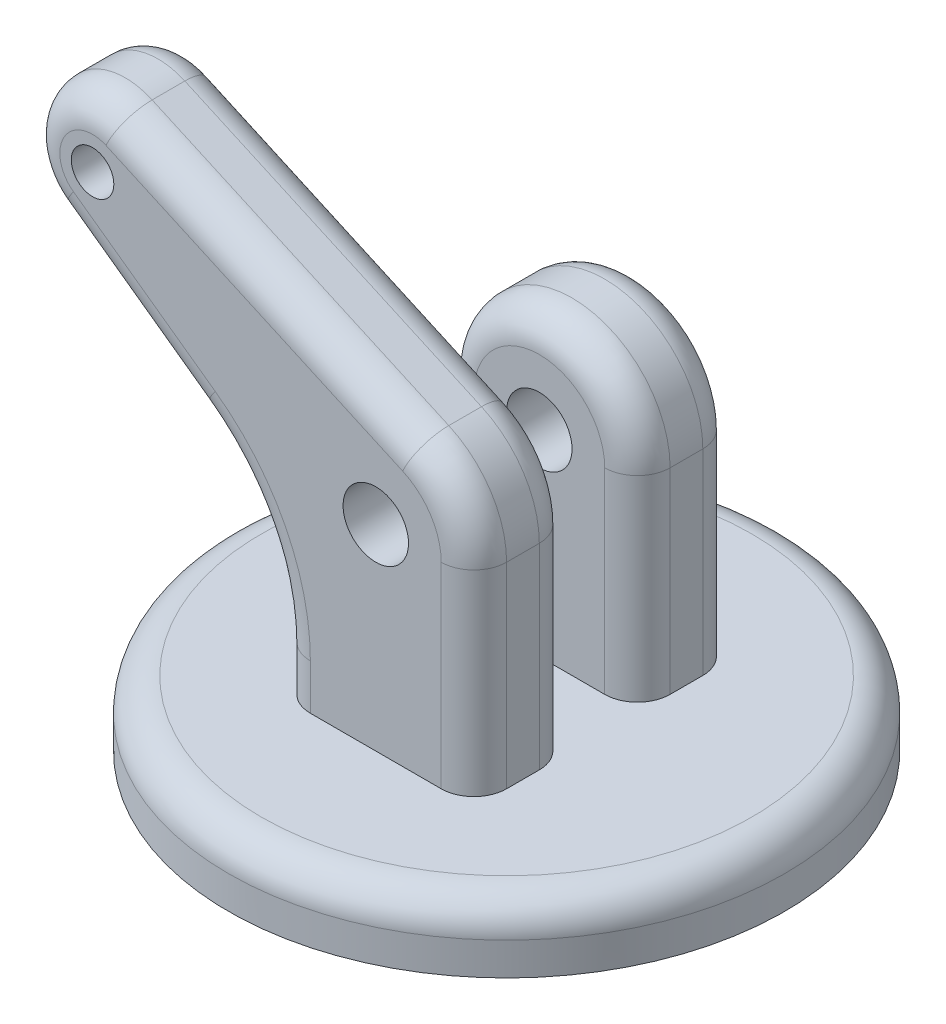
SolidWorks part; units mm, degrees
ref_plane "Front Plane" through (0, 0, 0) normal (0, 0, 1) x (1, 0, 0)
ref_plane "Top Plane" through (0, 0, 0) normal (0, 1, 0) x (1, 0, 0)
ref_plane "Right Plane" through (0, 0, 0) normal (1, 0, 0) x (0, 0, -1)
sketch "Sketch1" plane through (0, 0, 0) normal (0, 1, 0) x (1, 0, 0)
  line L1 (-20, 30) -> (20, 30)
  line L2 (-20, 30) -> (-20, -30)
  line L3 (-20, -30) -> (20, -30)
  line L4 (20, 30) -> (20, -30)
  line L5 (-20, 30) -> (20, -30) construction
  line L6 (-20, -30) -> (20, 30) construction
  point P0 (0, 0)
  dimension "D1" = 40
  dimension "D2" = 60
extrude "Boss-Extrude1" add sketch "Sketch1" along normal blind 10
sketch "Sketch2" plane through (0, 0, 0) normal (0, 1, 0) x (1, 0, 0)
  line L0 (-20, 0) -> (20, 0) construction
  line L1 (-20, 30) -> (-20, -30) construction
  line L2 (20, -30) -> (20, 30) construction
  line L4 (-15, 20) -> (15, 20)
  line L5 (-15, 20) -> (-15, -20)
  line L6 (-15, -20) -> (15, -20)
  line L7 (15, 20) -> (15, -20)
  line L8 (-15, 20) -> (15, -20) construction
  line L9 (-15, -20) -> (15, 20) construction
  point P6 (0, 0)
  dimension "D1" = 30
  dimension "D2" = 40
extrude "Boss-Extrude2" add sketch "Sketch2" along normal blind 40
sketch "Sketch6" plane through (0, 0, 0) normal (0, 0, 1) x (1, 0, 0)
  line L0 (-15, 40) -> (15, 40) construction
  circle A0 centre (0, 40) radius 15
  circle A1 centre (0, 40) radius 5
  dimension "D1" = 10
extrude "Boss-Extrude4" add sketch "Sketch6" against normal mid plane 40
sketch "Sketch7" plane through (0, 0, 0) normal (0, 0, 1) x (1, 0, 0)
  line L0 (-5, 40) -> (5, 40) construction
  circle A0 centre (0, 40) radius 5
extrude "Cut-Extrude2" cut sketch "Sketch7" against normal mid plane 60
sketch "Sketch8" plane through (0, 0, 0) normal (0, 1, 0) x (1, 0, 0)
  line L0 (-15, 0) -> (15, 0) construction
  line L1 (-15, -20) -> (-15, 20) construction
  line L2 (15, 20) -> (15, -20) construction
  line L4 (-15, 5) -> (15, 5)
  line L5 (-15, 5) -> (-15, -5)
  line L6 (-15, -5) -> (15, -5)
  line L7 (15, 5) -> (15, -5)
  line L8 (-15, 5) -> (15, -5) construction
  line L9 (-15, -5) -> (15, 5) construction
  point P6 (0, 0)
  dimension "D1" = 10
extrude "Cut-Extrude3" cut sketch "Sketch8" along normal blind 50 from surface starting at face at (0, 10, 0)
sketch "Sketch10" plane through (0, 0, 0) normal (0, 0, 1) x (1, 0, 0)
  line L0 (0, 40) -> (-66.6019, 40) construction
  line L1 (0, 40) -> (-43.3013, 65) construction
  line L2 (-49.1422, 56.8832) -> (-8.7614, 27.8247)
  line L3 (-39.1924, 74.1168) -> (6.1634, 53.6753)
  arc A0 (-39.1924, 74.1168) -> (-49.1422, 56.8832) centre (-43.3013, 65) ccw
  circle A1 centre (-43.3013, 65) radius 3.25
  circle A2 centre (0, 40) radius 15 construction
  arc A3 (-8.7614, 27.8247) -> (6.1634, 53.6753) centre (0, 40) cw
  dimension "D3" = 20
  dimension "D4" = 6.5
  dimension "D1" = 30
  dimension "D2" = 50
extrude "Boss-Extrude5" add sketch "Sketch10" along normal blind 15 from surface starting at face at (0, 28.75, 5)
fillet "Fillet1" radius 30 1 edges at (-15, 32.3141, 12.5)
fillet "Fillet2" radius 5 14 edges at (-15, 13.4711, 5) (-18.3009, 30.6227, 5) (-38.3097, 49.0879, 5) (-51.9615, 70, 5) (15, 25, 5) (12.5986, 48.1409, 5) (-15, 13.4711, 20) (-18.3009, 30.6227, 20) (-38.3097, 49.0879, 20) (-51.9615, 70, 20) (15, 25, 20) (12.5986, 48.1409, 20) (-16.5145, 63.8961, 5) (-16.5145, 63.8961, 20)
fillet "Fillet3" radius 5 6 edges at (15, 25, -20) (-15, 25, -20) (15, 25, -5) (-15, 25, -5) (0, 55, -20) (0, 55, -5)
fillet "Fillet4" radius 5 4 edges at (0, 10, -30) (20, 10, 0) (0, 10, 30) (-20, 10, 0)
fillet "Fillet5" radius 5 8 edges at (-18.5355, 8.5355, -28.5355) (18.5355, 8.5355, -28.5355) (18.5355, 8.5355, 28.5355) (-18.5355, 8.5355, 28.5355) (-20, 2.5, -30) (20, 2.5, -30) (20, 2.5, 30) (-20, 2.5, 30)
scale "缩放比例1" scale about centroid uniform scaling yes scale factor 2
sketch "草图1" plane through (0, -27.3139, 0) normal (0, -1, 0) x (1, 0, 0)
  line L0 (5.8557, 57.3632) -> (5.8557, -149.5906) construction
  line L1 (-24.1443, 57.3632) -> (35.8557, 57.3632) construction
  line L2 (-34.1443, -2.6368) -> (157.2212, -2.6368) construction
  line L3 (-34.1443, -52.6368) -> (-34.1443, 47.3632) construction
  circle A0 centre (5.8557, -2.6368) radius 85
  dimension "D2" = 170
  dimension "D1" = 40
extrude "凸台-拉伸1" add sketch "草图1" against normal blind 20
fillet "圆角1" radius 10 1 edges at (5.8557, -7.3139, -87.6368) type face fillet first side face at (5.8557, -7.3139, -87.6368) second side face at (5.8557, -7.3139, 22.3632)
